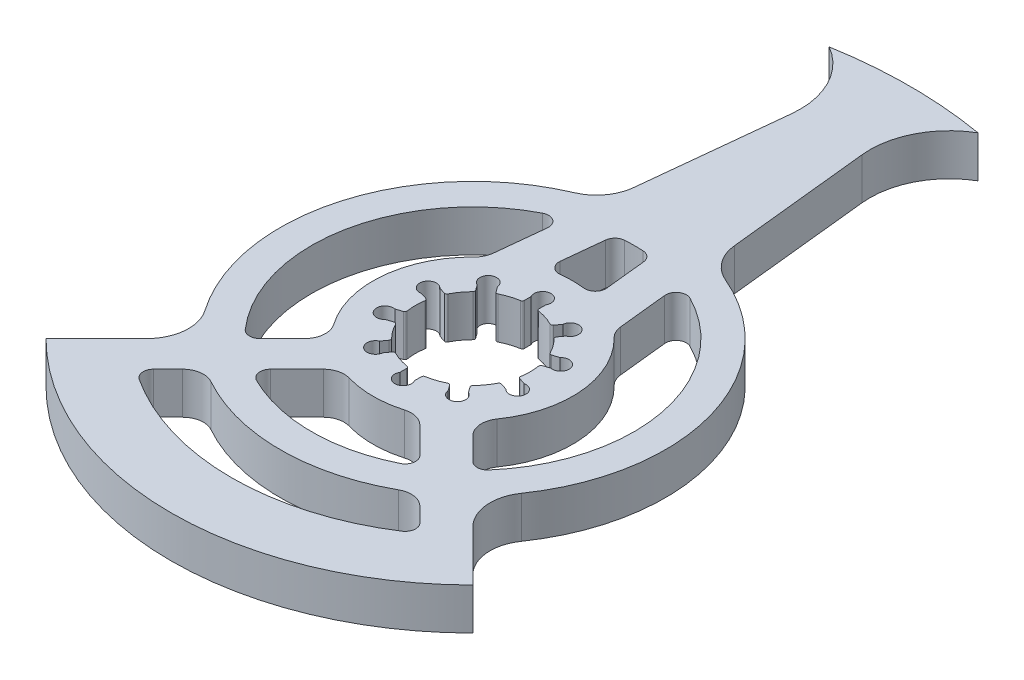
SolidWorks part; units mm, degrees
material "AISI Type A2 Tool Steel"
ref_plane "Front Plane" through (0, 0, 0) normal (0, 0, 1) x (1, 0, 0)
ref_plane "Top Plane" through (0, 0, 0) normal (0, 1, 0) x (1, 0, 0)
ref_plane "Right Plane" through (0, 0, 0) normal (1, 0, 0) x (0, 0, -1)
other "Center of Mass"
other "Bounding Box"
ref_plane "Default Plane" through (0, 2.286, 19.05) normal (0, -1, 0) x (-1, 0, 0)
sketch "Sketch1" plane through (0, 0, 0) normal (0, 1, 0) x (1, 0, 0)
  circle A0 centre (0, 0) radius 133.35 construction
  circle A1 centre (0, 0) radius 30.48
  circle A2 centre (0, 0) radius 17.4625
  dimension "D1" = 266.7
  dimension "D2" = 60.96
  dimension "D3" = 34.925
extrude "Boss-Extrude1" add sketch "Sketch1" along normal mid plane 12.7
sketch "Sketch2" plane through (0, 6.35, 0) normal (0, 1, 0) x (1, 0, 0)
  line L0 (-10.795, 107.95) -> (-19.6961, 23.2614)
  line L1 (19.6961, 23.2614) -> (10.795, 107.95)
  line L4 (0, 0) -> (0, 133.35) construction
  line L5 (-10.795, 107.95) -> (0, 107.95) construction
  line L6 (0, 107.95) -> (10.795, 107.95) construction
  line L7 (-22.6939, 131.4048) -> (0, 0) construction
  line L8 (-22.6939, 131.4048) -> (125.4677, 45.1673) construction
  circle A0 centre (0, 0) radius 133.35 construction
  circle A1 centre (0, 0) radius 133.35 construction
  arc A2 (-22.6939, 131.4048) -> (22.6939, 131.4048) centre (0, 0) cw
  arc A3 (-22.6939, 131.4048) -> (-10.795, 107.95) centre (-34.8727, 110.4807) cw
  circle A5 centre (0, 0) radius 30.48
  arc A6 (19.6961, 23.2614) -> (-19.6961, 23.2614) centre (0, 0) ccw
  arc A7 (-19.6961, 23.2614) -> (19.6961, 23.2614) centre (0, 0) ccw construction
  arc A8 (10.795, 107.95) -> (22.6939, 131.4048) centre (34.8727, 110.4807) cw
  dimension "D4" = 25.4
  dimension "D5" = 6
  dimension "D6" = 10.795
  dimension "D1" = 50
  dimension "D2" = 0
extrude "Boss-Extrude2" add sketch "Sketch2" against normal through all
sketch "Sketch3" plane through (0, 6.35, 0) normal (0, 1, 0) x (1, 0, 0)
  line L0 (-65.1069, -65.1069) -> (-21.5526, -21.5526)
  line L1 (21.5526, -21.5526) -> (65.1069, -65.1069)
  line L2 (0, -30.48) -> (0, -92.075) construction
  line L4 (-21.5526, -21.5526) -> (0, 0) construction
  line L5 (0, 0) -> (21.5526, -21.5526) construction
  arc A0 (-65.1069, -65.1069) -> (65.1069, -65.1069) centre (0, 0) ccw
  circle A1 centre (0, 0) radius 30.48 construction
  arc A3 (-21.5526, -21.5526) -> (21.5526, -21.5526) centre (0, 0) ccw
  point P13 (0, -92.075)
  dimension "D2" = 92.075
  dimension "D1" = 90
extrude "Boss-Extrude3" add sketch "Sketch3" against normal through all
sketch "Sketch5" plane through (0, 6.35, 0) normal (0, 1, 0) x (1, 0, 0)
  line L0 (0, 17.4625) -> (0, 21.2725) construction
  line L2 (-2.2225, 17.3205) -> (2.2225, 17.3205)
  line L3 (-2.2225, 17.3205) -> (-2.2225, 20.0168)
  line L5 (2.2225, 17.3205) -> (2.2225, 20.0168)
  arc A0 (2.2225, 20.0168) -> (-2.2225, 20.0168) centre (0, 21.2725) ccw
  circle A1 centre (0, 0) radius 17.4625 construction
  circle A2 centre (0, 21.2725) radius 4.5847 construction
  dimension "D2" = 5.1054
  dimension "D4" = 9.1694
  dimension "D1" = 3.81
  dimension "D3" = 4.445
extrude "Cut-Extrude2" cut sketch "Sketch5" against normal through all
pattern_circular "CirPattern1" count 10 over 360 about axis through (0, 6.35, 0) along (0, -1, 0) of "Cut-Extrude2"
sketch "Sketch6" plane through (0, 6.35, 0) normal (0, 1, 0) x (1, 0, 0)
  circle A0 centre (0, 0) radius 17.526
  arc A1 (-11.9788, 12.7062) -> (-15.786, 7.466) centre (0, 0) ccw construction
  dimension "D1" = 0.0635
extrude "Cut-Extrude3" cut sketch "Sketch6" against normal through all
sketch "Sketch7" plane through (0, 6.35, 0) normal (0, 1, 0) x (1, 0, 0)
  line L0 (-43.3087, -59.4732) -> (-11.8976, -28.062)
  line L1 (11.8976, -28.062) -> (43.3087, -59.4732)
  line L3 (-21.5526, -21.5526) -> (-65.1069, -65.1069) construction
  line L4 (65.1069, -65.1069) -> (21.5526, -21.5526) construction
  line L5 (-43.3087, -59.4732) -> (-51.391, -51.391) construction
  line L6 (43.3087, -59.4732) -> (51.391, -51.391) construction
  arc A0 (-11.8976, -28.062) -> (11.8976, -28.062) centre (0, 0) ccw
  arc A1 (-43.3087, -59.4732) -> (43.3087, -59.4732) centre (0, 0) ccw
  arc A2 (-65.1069, -65.1069) -> (65.1069, -65.1069) centre (0, 0) ccw construction
  arc A4 (21.5526, -21.5526) -> (19.6961, 23.2614) centre (0, 0) ccw construction
  dimension "D1" = 18.5039
  dimension "D2" = 11.43
extrude "Cut-Extrude4" cut sketch "Sketch7" against normal through all
sketch "Sketch8" plane through (0, 6.35, 0) normal (0, 1, 0) x (1, 0, 0)
  circle A0 centre (0, 0) radius 49.2125
  circle A1 centre (0, 0) radius 58.7375
  dimension "D1" = 9.525
  dimension "D2" = 117.475
extrude "Boss-Extrude4" add sketch "Sketch8" against normal through all
sketch "Sketch11" plane through (0, 6.35, 0) normal (0, 1, 0) x (1, 0, 0)
  line L0 (-7.5441, 29.5316) -> (-5.5081, 48.9033)
  line L1 (5.5081, 48.9033) -> (7.5441, 29.5316)
  line L3 (-17.2986, 46.072) -> (-19.6961, 23.2614) construction
  line L4 (19.6961, 23.2614) -> (17.2986, 46.072) construction
  line L5 (-6.5261, 39.2174) -> (-17.8935, 40.4122) construction
  line L6 (6.5261, 39.2174) -> (17.8935, 40.4122) construction
  arc A0 (-7.5441, 29.5316) -> (7.5441, 29.5316) centre (0, 0) cw
  arc A1 (-5.5081, 48.9033) -> (5.5081, 48.9033) centre (0, 0) cw
  arc A2 (-19.6961, 23.2614) -> (-21.5526, -21.5526) centre (0, 0) ccw construction
  arc A3 (-17.2986, 46.072) -> (-34.7985, -34.7985) centre (0, 0) ccw construction
  dimension "D1" = 11.43
extrude "Cut-Extrude6" cut sketch "Sketch11" against normal through all
fillet "Fillet1" radius 6.35 8 edges at (-21.5526, 0, 21.5526) (21.5526, 0, 21.5526) (19.6961, 0, -23.2614) (-19.6961, 0, -23.2614) (11.8976, 0, 28.062) (-11.8976, 0, 28.062) (32.6575, 0, 48.8219) (-32.6575, 0, 48.8219)
fillet "Fillet6" radius 0.635 20 edges at (-12.0164, 0, -12.758) (-15.8469, 0, -7.4858) (-17.2204, 0, -3.2584) (-17.2204, 0, 3.2584) (-15.8469, 0, 7.4858) (-12.0164, 0, 12.758) (-8.4203, 0, 15.3707) (-2.2225, 0, 17.3845) (2.2225, 0, 17.3845) (8.4203, 0, 15.3707) (12.0164, 0, 12.758) (15.8469, 0, 7.4858) (17.2204, 0, 3.2584) (17.2204, 0, -3.2584) (15.8469, 0, -7.4858) (12.0164, 0, -12.758) (8.4203, 0, -15.3707) (2.2225, 0, -17.3845) (-2.2225, 0, -17.3845) (-8.4203, 0, -15.3707)
fillet "Fillet7" radius 3.175 12 edges at (-25.7647, 0, 41.9291) (25.7647, 0, 41.9291) (34.7985, 0, 34.7985) (-34.7985, 0, 34.7985) (-17.2986, 0, -46.072) (17.2986, 0, -46.072) (43.3087, 0, 59.4732) (-43.3087, 0, 59.4732) (-7.5441, 0, -29.5316) (7.5441, 0, -29.5316) (5.5081, 0, -48.9033) (-5.5081, 0, -48.9033)
fillet "Fillet8" radius 12.7 4 edges at (-16.2071, 0, -56.4573) (16.2071, 0, -56.4573) (41.5337, 0, 41.5337) (-41.5337, 0, 41.5337)
sketch "Sketch12" plane through (0, -6.35, 0) normal (0, -1, 0) x (1, 0, 0)
  line L0 (-58.7375, 0) -> (-53.975, 0) construction
  line L1 (-53.975, 0) -> (-49.2125, 0) construction
  circle A0 centre (0, 0) radius 53.975
  arc A1 (-48.2558, 33.4883) -> (-23.0251, -54.0365) centre (0, 0) ccw construction
  arc A2 (-37.1155, 32.3157) -> (-22.4793, -43.7784) centre (0, 0) ccw construction
equation "\"Unit Measure\"= \"BoundingVolume\" / \"Thickness\"'in^2"
